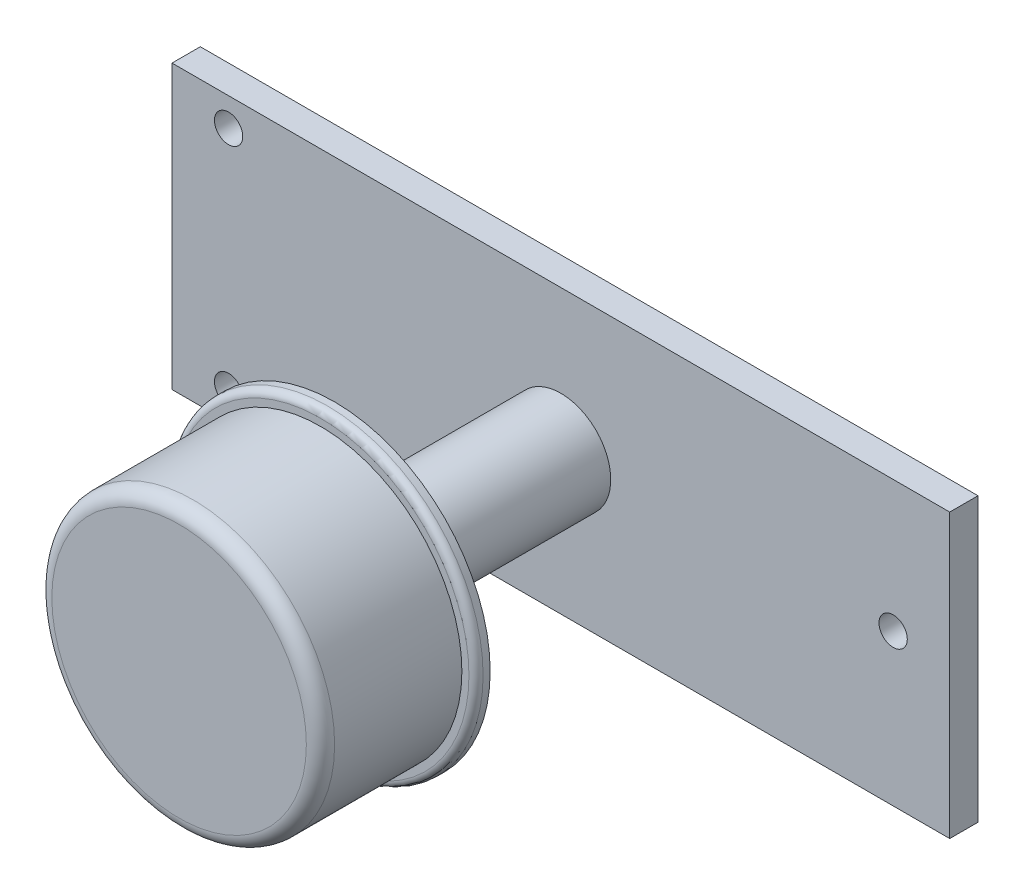
SolidWorks part; units mm, degrees
ref_plane "Front Plane" through (0, 0, 0) normal (0, 0, 1) x (1, 0, 0)
ref_plane "Top Plane" through (0, 0, 0) normal (0, 1, 0) x (1, 0, 0)
ref_plane "Right Plane" through (0, 0, 0) normal (1, 0, 0) x (0, 0, -1)
sketch "Sketch1" plane through (0, 0, 0) normal (0, 0, 1) x (1, 0, 0)
  line L1 (0, 0) -> (55, 0)
  line L2 (0, 0) -> (0, 20)
  line L3 (0, 20) -> (55, 20)
  line L4 (55, 0) -> (55, 20)
  circle A0 centre (4, 18) radius 1
  circle A1 centre (4, 2) radius 1
  circle A2 centre (51, 10.7109) radius 1
  point P11 (0, 0)
  dimension "D7" = 2
  dimension "D8" = 2
  dimension "D9" = 2
  dimension "D1" = 20
  dimension "D2" = 55
  dimension "D3" = 47
  dimension "D4" = 4
  dimension "D5" = 2
  dimension "D6" = 2
extrude "Boss-Extrude1" add sketch "Sketch1" along normal blind 2
sketch "Sketch2" plane through (0, 0, 2) normal (0, 0, 1) x (1, 0, 0)
  line L0 (55, 20) -> (0, 20) construction
  line L1 (55, 0) -> (55, 20) construction
  circle A0 centre (27.5, 10) radius 3.5266
  point P2 (0, 0)
  point P5 (27.5, 20)
  point P8 (55, 10)
extrude "Boss-Extrude2" add sketch "Sketch2" along normal blind 16
sketch "Sketch3" plane through (0, 0, 18) normal (0, 0, 1) x (1, 0, 0)
  circle A0 centre (27.5, 10) radius 11
  dimension "D1" = 22
extrude "Boss-Extrude3" add sketch "Sketch3" along normal blind 1
sketch "Sketch5" plane through (0, 0, 19) normal (0, 0, 1) x (1, 0, 0)
  circle A0 centre (27.5, 10) radius 10
extrude "Boss-Extrude4" add sketch "Sketch5" along normal blind 10
fillet "Fillet1" radius 1 1 edges at (37.5, 10, 29)
fillet "Fillet2" radius 0.5 1 edges at (38.5, 10, 19)
